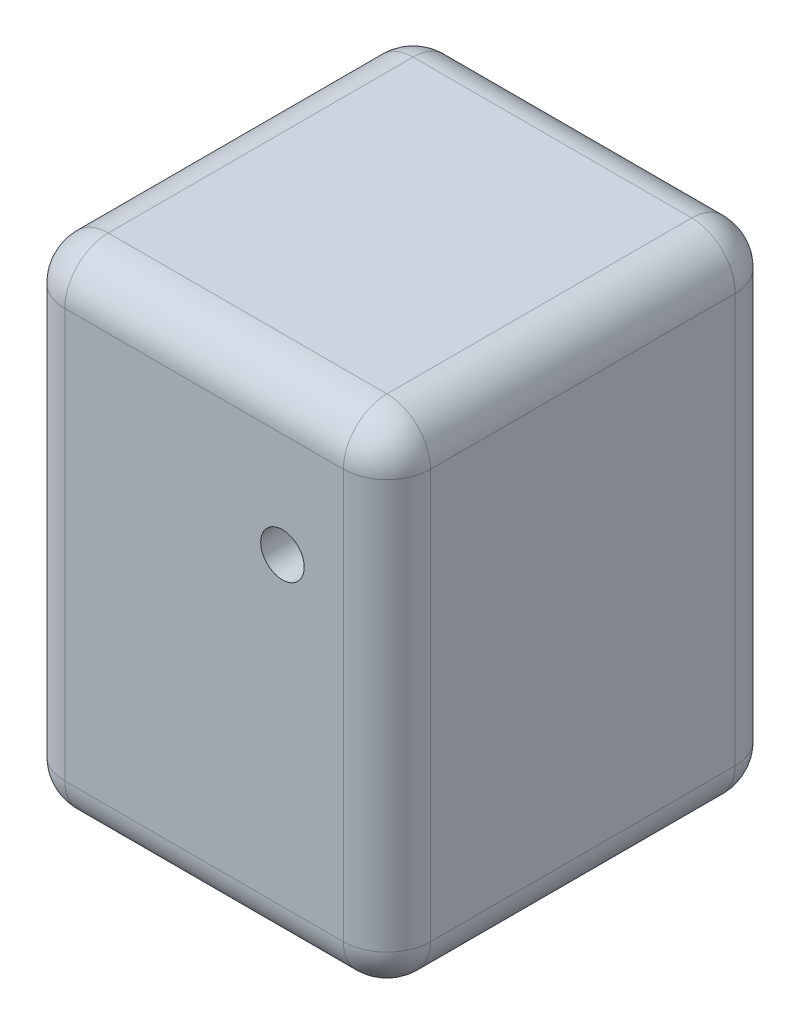
SolidWorks part; units mm, degrees
material "ABS"
ref_plane "Front Plane" through (0, 0, 0) normal (0, 0, 1) x (1, 0, 0)
ref_plane "Top Plane" through (0, 0, 0) normal (0, 1, 0) x (1, 0, 0)
ref_plane "Right Plane" through (0, 0, 0) normal (1, 0, 0) x (0, 0, -1)
sketch "Sketch1" plane through (0, 0, 0) normal (0, 0, 1) x (1, 0, 0)
  line L0 (0, 0) -> (0, 17) construction
  line L1 (0, 0) -> (-30, 0) construction
  line L2 (0, 17) -> (-30, 17) construction
  line L4 (-30, 17) -> (12, 17)
  line L5 (-30, 17) -> (-30, -40)
  line L6 (-30, -40) -> (12, -40)
  line L7 (12, 17) -> (12, -40)
  circle A0 centre (0, 0) radius 2.5
extrude "Boss-Extrude1" add sketch "Sketch1" along normal blind 45
fillet "Fillet1" radius 5 11 edges at (-30, 17, 22.5) (-30, -40, 22.5) (-30, -11.5, 0) (-9, 17, 45) (-9, -40, 45) (-30, -11.5, 45) (12, -40, 22.5) (12, -11.5, 45) (12, 17, 22.5) (12, -11.5, 0) (-9, 17, 0)
fillet "Fillet2" radius 5 3 edges at (-28.5355, -38.5355, 1.4645) (10.5355, -38.5355, 1.4645) (-9, -40, 0)
sketch "Sketch2" plane through (-30, 0, 0) normal (-1, 0, 0) x (0, 0, 1)
  circle A0 centre (22.5, -11.5) radius 10
  circle A1 centre (22.5, -11.5) radius 2.5
extrude "Boss-Extrude2" add sketch "Sketch2" along normal blind 1
fillet "Fillet3" radius 1 1 edges at (-31, -11.5, 32.5)
ref_axis "Axis1" through (0, 0, 45) along (0, 0, -1)
ref_axis "Axis2" through (-31, -11.5, 22.5) along (1, 0, 0)
ref_point "Point1"
ref_plane "Plane1" through (7, 17, 5) normal (0, 0, -1) x (-1, 0, 0)
ref_plane "Plane2" through (0, 0, 22.5) normal (0, 0, -1) x (-1, 0, 0)
ref_point "Point2"
ref_point "Point3"
